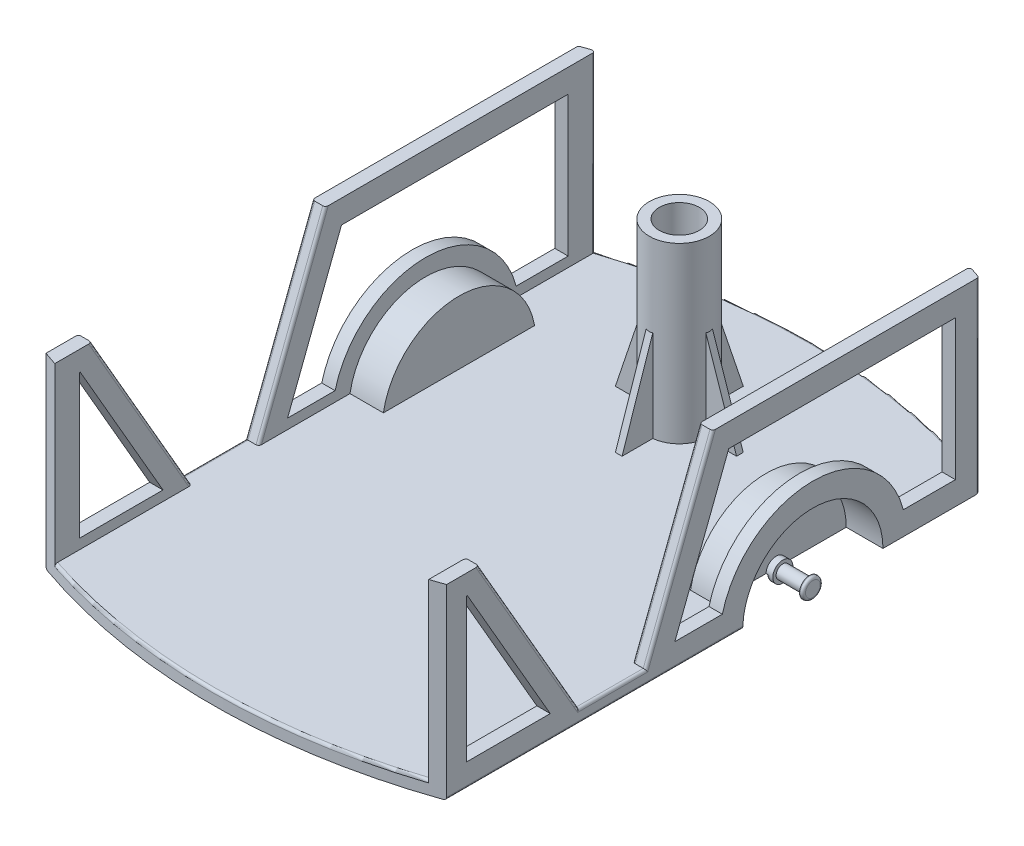
SolidWorks part; units mm, degrees
ref_plane "前视基准面" through (0, 0, 0) normal (0, 0, 1) x (1, 0, 0)
ref_plane "上视基准面" through (0, 0, 0) normal (0, 1, 0) x (1, 0, 0)
ref_plane "右视基准面" through (0, 0, 0) normal (1, 0, 0) x (0, 0, -1)
sketch "草图2" plane through (0, 0, 0) normal (1, 0, 0) x (0, 0, -1)
  line L0 (10, 0) -> (300, 0)
  line L1 (300, 0) -> (300, 300)
  line L2 (300, 300) -> (-600, 300)
  line L3 (-600, 300) -> (-600, 0)
  line L4 (-600, 0) -> (-10, 0)
  arc A0 (-10, 0) -> (10, 0) centre (0, 0) ccw
  dimension "D1" = 20
  dimension "D2" = 290
  dimension "D3" = 590
  dimension "D4" = 900
  dimension "D5" = 300
  dimension "D6" = 300
extrude "车身" add sketch "草图2" along normal blind 300 and the other way blind 300
sketch "草图3" plane through (300, 0, 0) normal (1, 0, 0) x (0, 0, -1)
  circle A0 centre (0, 0) radius 105
  circle A1 centre (0, 0) radius 10
  dimension "D1" = 210
  dimension "D2" = 20
extrude "前轮轮胎" cut sketch "草图3" against normal blind 55
sketch "草图4" plane through (300, 0, 0) normal (1, 0, 0) x (0, 0, -1)
  circle A0 centre (0, 0) radius 15
  dimension "D1" = 30
extrude "轮胎固定1" add sketch "草图4" against normal blind 5
sketch "草图5" plane through (245, 0, 0) normal (1, 0, 0) x (0, 0, -1)
  circle A0 centre (0, 0) radius 15
  dimension "D1" = 30
extrude "轮胎固定2" add sketch "草图5" along normal blind 10
mirror "镜向1" about plane through (0, 0, 0) normal (1, 0, 0) of "轮胎固定2", "轮胎固定1", "前轮轮胎"
sketch "草图7" plane through (0, 300, 0) normal (0, 1, 0) x (1, 0, 0)
  line L1 (-1045.7627, 400) -> (1045.7627, 400)
  line L2 (-1045.7627, 400) -> (-1045.7627, -1600)
  line L3 (-1045.7627, -1600) -> (1045.7627, -1600)
  line L4 (1045.7627, 400) -> (1045.7627, -1600)
  line L5 (-1045.7627, 400) -> (1045.7627, -1600) construction
  line L6 (-1045.7627, -1600) -> (1045.7627, 400) construction
  arc A0 (779.4229, -150) -> (-779.4229, -150) centre (0, -600) ccw
  arc A2 (-779.4229, -150) -> (779.4229, -150) centre (0, 300) ccw
  dimension "D2" = 1800
  dimension "D1" = 600
  dimension "D3" = 1000
  dimension "D5" = 300
extrude "切除-拉伸3" cut sketch "草图7" against normal through all
sketch "草图9" plane through (0, 0, 0) normal (1, 0, 0) x (0, 0, -1)
  line L0 (-900, 420) -> (-900, 20)
  line L1 (-900, 20) -> (300, 20)
  line L2 (300, 20) -> (300, 420)
  line L3 (-900, 420) -> (300, 420)
  line L4 (-548.5281, 0) -> (-105, 0) construction
  dimension "D1" = 20
  dimension "D2" = 300
  dimension "D3" = 900
  dimension "D4" = 400
extrude "切除-拉伸4" cut sketch "草图9" against normal blind 230 and the other way blind 230
sketch "草图11" plane through (0, 0, 0) normal (1, 0, 0) x (0, 0, -1)
  line L0 (113.2475, 20) -> (300, 20)
  line L1 (300, 20) -> (300, 400)
  line L2 (300, 400) -> (-900, 400)
  line L3 (-900, 400) -> (-900, 20)
  line L4 (-900, 20) -> (-113.2475, 20)
  line L5 (-548.5281, 0) -> (-105, 0) construction
  arc A0 (113.2475, 20) -> (-113.2475, 20) centre (0, 0) ccw
  dimension "D1" = 230
  dimension "D2" = 400
  dimension "D3" = 900
  dimension "D4" = 300
  dimension "D5" = 20
extrude "切除-拉伸5" cut sketch "草图11" against normal blind 280 and the other way blind 280
sketch "草图12" plane through (0, 0, 0) normal (1, 0, 0) x (0, 0, -1)
  line L2 (300, 280) -> (-150, 280)
  line L4 (-548.5281, 0) -> (-105, 0) construction
  line L5 (300, 280) -> (300, 310)
  line L6 (300, 310) -> (-800, 310)
  line L8 (-800, 310) -> (-800, 280)
  line L9 (-548.5281, 0) -> (-105, 0) construction
  line L15 (-500, 280) -> (-350, 20)
  line L16 (-350, 20) -> (-250, 20)
  line L17 (-250, 20) -> (-150, 280)
  line L18 (-500, 280) -> (-800, 280)
  line L19 (-1500, 0) -> (248.5281, 0) construction
  dimension "D2" = 280
  dimension "D3" = 20
  dimension "D4" = 350
  dimension "D5" = 150
  dimension "D6" = 500
  dimension "D7" = 310
  dimension "D8" = 300
  dimension "D1" = 250
  dimension "D9" = 800
extrude "切除-拉伸6" cut sketch "草图12" against normal blind 310 and the other way blind 310
sketch "草图13" plane through (300, 0, 0) normal (1, 0, 0) x (0, 0, -1)
  line L9 (213.5281, 35) -> (213.5281, 245)
  line L10 (213.5281, 35) -> (213.5281, 245)
  line L11 (135.5544, 35) -> (213.5281, 35)
  line L12 (135.5544, 35) -> (213.5281, 35)
  line L27 (-206.7313, 35) -> (-135.5544, 35)
  line L29 (213.5281, 245) -> (-125.962, 245)
  line L30 (-125.962, 245) -> (-206.7313, 35)
  line L31 (-206.7313, 35) -> (-135.5544, 35)
  line L33 (213.5281, 245) -> (-125.962, 245)
  line L34 (-125.962, 245) -> (-206.7313, 35)
  arc A3 (135.5544, 35) -> (-135.5544, 35) centre (0, 0) ccw
  arc A4 (135.5544, 35) -> (-135.5544, 35) centre (0, 0) ccw
  dimension "D1" = 35
extrude "切除-拉伸7" cut sketch "草图13" against normal blind 700
sketch "草图14" plane through (300, 0, 0) normal (1, 0, 0) x (0, 0, -1)
  line L0 (-518.5281, 35) -> (-393.2885, 35)
  line L1 (-393.2885, 35) -> (-517.3269, 250)
  line L2 (-517.3269, 250) -> (-518.5281, 250)
  line L3 (-518.5281, 250) -> (-518.5281, 35)
  line L4 (-350, 20) -> (-500, 280) construction
  line L5 (-500, 280) -> (-548.5281, 280) construction
  line L6 (-548.5281, 280) -> (-548.5281, 0) construction
  line L7 (-548.5281, 0) -> (-105, 0) construction
  dimension "D1" = 30
  dimension "D2" = 30
  dimension "D3" = 30
  dimension "D4" = 35
extrude "切除-拉伸8" cut sketch "草图14" against normal blind 700
sketch "草图16" plane through (0, 20, 0) normal (0, 1, 0) x (1, 0, 0)
  circle A0 centre (0, 100) radius 45
  circle A1 centre (0, 100) radius 30
  point P4 (0, 0)
  point P5 (0, 0)
  dimension "D1" = 90
  dimension "D2" = 60
  dimension "D3" = 100
extrude "凸台-拉伸4" add sketch "草图16" along normal blind 260
ref_axis "基准轴1" through (0, 280, -100) along (0, -1, 0)
sketch "草图20" plane through (0, 0, 0) normal (1, 0, 0) x (0, 0, -1)
  line L0 (190.8032, 20) -> (138.8565, 174.5999)
  line L1 (138.8565, 174.5999) -> (138.8565, 20)
  line L2 (138.8565, 20) -> (190.8032, 20)
extrude "凸台-拉伸8" add sketch "草图20" along normal blind 5 and the other way blind 5
pattern_circular "阵列(圆周)1" count 4 over 360 about axis through (0, 280, -100) along (0, -1, 0) of "凸台-拉伸8"
sketch "草图18" plane through (0, 0, 0) normal (0, -1, 0) x (1, 0, 0)
  circle A0 centre (0, 400) radius 30
  dimension "D1" = 60
  dimension "D2" = 400
  dimension "D3" = 0
extrude "凸台-拉伸6" add sketch "草图18" along normal blind 10
fillet "圆角1" radius 4 23 edges at (-300, 0, 326.7641) (300, 0, 326.7641) (0, 20, -300) (-300, 20, 300) (300, 20, 300) (0, 0, -300) (-300, 140, -248.5281) (-280, 150, -255.3362) (280, 150, -255.3362) (300, 140, -248.5281) (245, -15, 0) (-245, -15, 0) (-300, 0, -15) (300, 0, -15) (-300, 150, 425) (-280, 150, 425) (-300, 150, 200) (-280, 150, 200) (280, 150, 200) (300, 150, 200) (280, 150, 425) (300, 150, 425) (0, 20, 600)
sketch "草图19" plane through (0, -10, 0) normal (0, -1, 0) x (1, 0, 0)
  circle A0 centre (0, 400) radius 5
  dimension "D1" = 10
extrude "凸台-拉伸7" add sketch "草图19" along normal blind 10
